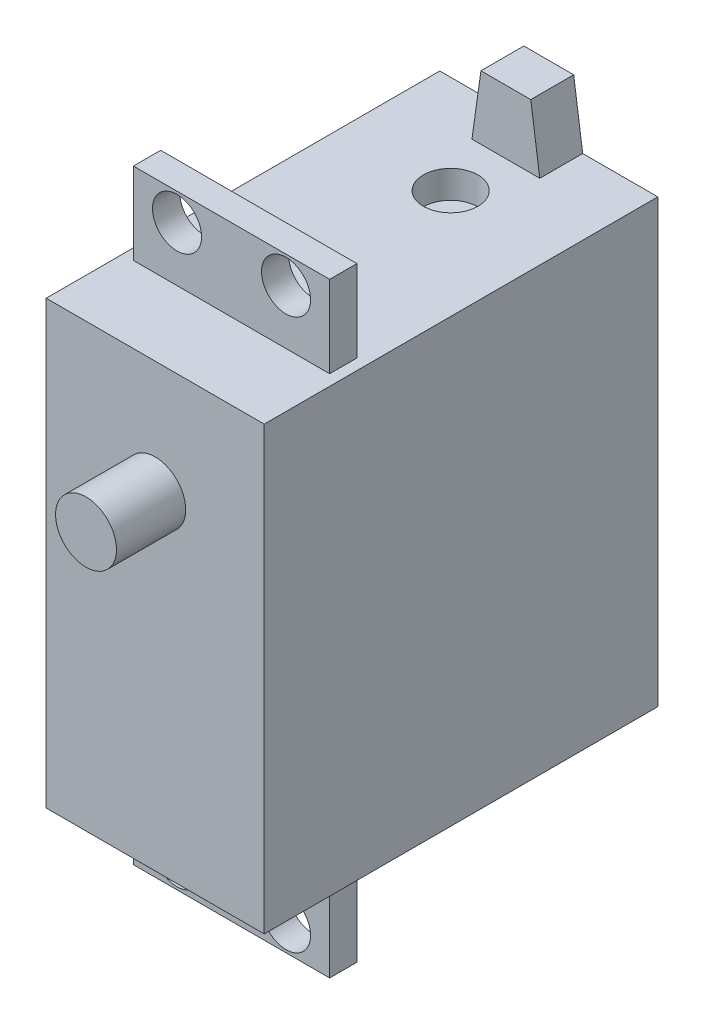
SolidWorks part; units mm, degrees
ref_plane "Front Plane" through (0, 0, 0) normal (0, 0, 1) x (1, 0, 0)
ref_plane "Top Plane" through (0, 0, 0) normal (0, 1, 0) x (1, 0, 0)
ref_plane "Right Plane" through (0, 0, 0) normal (1, 0, 0) x (0, 0, -1)
sketch "Sketch1" plane through (0, 0, 0) normal (0, 0, 1) x (1, 0, 0)
  line L1 (0, 40.5) -> (20, 40.5)
  line L2 (0, 40.5) -> (0, 0)
  line L3 (0, 0) -> (20, 0)
  line L4 (20, 40.5) -> (20, 0)
  dimension "D1" = 20
  dimension "D2" = 40.5
extrude "Boss-Extrude1" add sketch "Sketch1" along normal mid plane 19
sketch "Sketch2" plane through (0, 0, -9.5) normal (0, 0, -1) x (-1, 0, 0)
  line L0 (-20, 40.5) -> (0, 40.5) construction
  line L1 (-20, 40.5) -> (0, 40.5)
  line L2 (-20, 40.5) -> (-20, 0)
  line L3 (-20, 0) -> (0, 0)
  line L4 (0, 40.5) -> (0, 0)
  line L5 (-20, 0) -> (-20, 40.5) construction
  line L6 (0, 40.5) -> (0, 0) construction
extrude "Boss-Extrude2" add sketch "Sketch2" along normal blind 17.1
sketch "Sketch3" plane through (0, 0, 0) normal (0, 0, 1) x (1, 0, 0)
  line L0 (0, 0) -> (20, 0) construction
  line L1 (19, 0) -> (1, 0) construction
  line L2 (19, 0) -> (19, -7.5)
  line L3 (20, 40.5) -> (20, 0)
  line L4 (1, 0) -> (1, -7.5)
  line L5 (20, 40.5) -> (0, 40.5) construction
  line L6 (0, 40.5) -> (0, 0)
  line L7 (19, 48) -> (19, 40.5)
  line L8 (19, 40.5) -> (1, 40.5) construction
  line L9 (1, 48) -> (1, 40.5)
  line L10 (20, 0) -> (19, 0)
  line L11 (1, 0) -> (0, 0)
  line L12 (20, 40.5) -> (19, 40.5)
  line L13 (1, 40.5) -> (0, 40.5)
  line L14 (0, 40.5) -> (0, 0) construction
  line L15 (20, 0) -> (20, 40.5) construction
  line L19 (1, 48) -> (19, 48)
  line L20 (1, -7.5) -> (19, -7.5)
  line L24 (10, 48) -> (10, 45.5) construction
  line L25 (10, -7.5) -> (10, -5) construction
  line L28 (15, 45.5) -> (15, -5) construction
  line L29 (5, 45.5) -> (5, -5) construction
  line L30 (5, -5) -> (15, -5) construction
  line L31 (5, 45.5) -> (15, 45.5) construction
  circle A0 centre (5, -5) radius 2.25
  circle A1 centre (15, -5) radius 2.25
  circle A2 centre (5, 45.5) radius 2.25
  circle A3 centre (15, 45.5) radius 2.25
  dimension "D6" = 4.5
  dimension "D1" = 18
  dimension "D2" = 55.5
  dimension "D3" = 50.5
  dimension "D4" = 10
extrude "Boss-Extrude3" add sketch "Sketch3" along normal blind 2.5
sketch "Sketch4" plane through (0, 0, 9.5) normal (0, 0, 1) x (1, 0, 0)
  line L76 (0, 30.1) -> (20, 30.1) construction
  line L77 (0, 40.5) -> (0, 0) construction
  line L78 (20, 0) -> (20, 40.5) construction
  line L80 (20, 40.5) -> (0, 40.5) construction
  circle A0 centre (10, 30.1) radius 2.794
  dimension "D1" = 5.588
  dimension "D3" = 10.4
extrude "Boss-Extrude4" add sketch "Sketch4" along normal blind 6.349
sketch "Sketch6" plane through (0, 0, 2.5) normal (0, 0, 1) x (1, 0, 0)
  line L0 (5, 8.61) -> (5, -18.61) construction
  line L1 (1, -7.5) -> (19, -7.5) construction
  circle A0 centre (5, -5) radius 2.25 construction
  point P2 (5, -5)
sketch "Sketch7" plane through (0, 40.5, 0) normal (0, 1, 0) x (1, 0, 0)
  line L0 (10, 17.6) -> (10, 26.6) construction
  line L1 (0, 26.6) -> (20, 26.6) construction
  circle A0 centre (10, 17.6) radius 2.5
  dimension "D2" = 5
  dimension "D1" = 9
extrude "Cut-Extrude1" cut sketch "Sketch7" against normal blind 2.54
sketch "Sketch9" plane through (0, 0, -26.6) normal (0, 0, -1) x (-1, 0, 0)
  line L0 (0, 40.5) -> (-20, 40.5) construction
  line L1 (-13.1115, 40.5) -> (-6.8885, 40.5)
  line L2 (-13.1115, 40.5) -> (-12.286, 46.342)
  line L3 (-12.286, 46.342) -> (-7.714, 46.342)
  line L4 (-6.8885, 40.5) -> (-7.714, 46.342)
  line L5 (-10, 40.5) -> (-10, 46.342) construction
  point P4 (-10, 40.5)
  dimension "D1" = 6.223
  dimension "D2" = 4.572
  dimension "D3" = 5.842
extrude "Boss-Extrude6" add sketch "Sketch9" against normal blind 3.937
